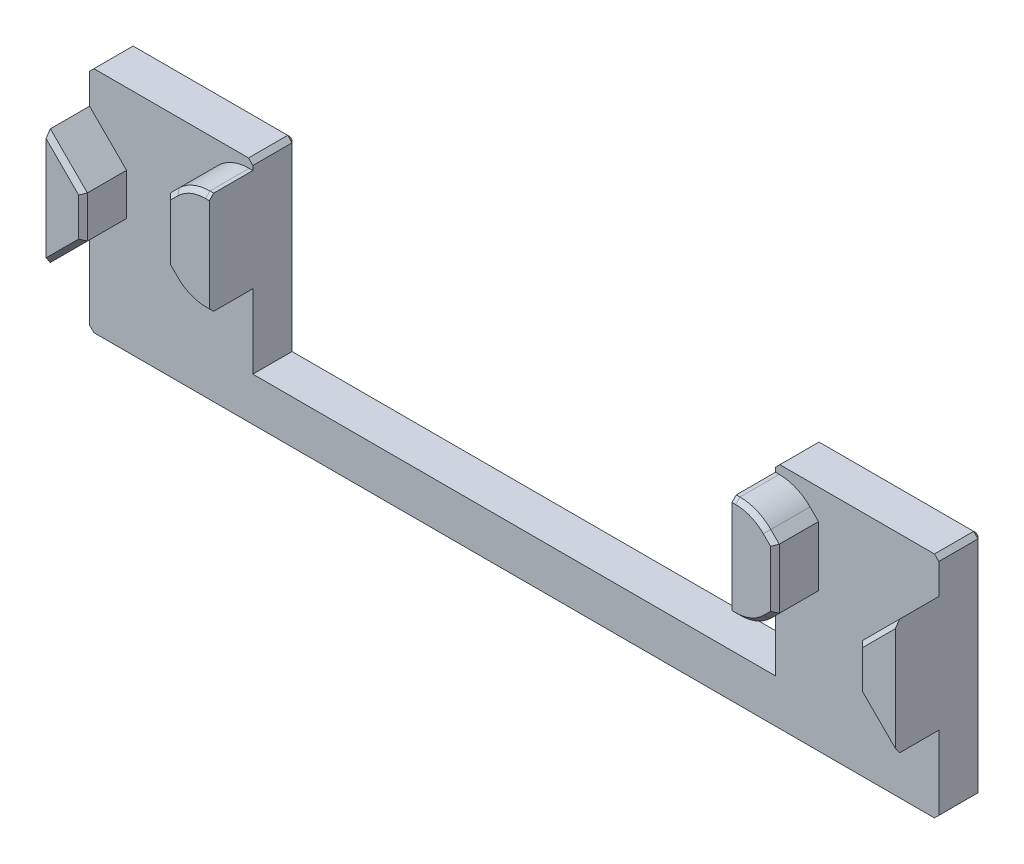
SolidWorks part; units mm, degrees
ref_plane "Front" through (0, 0, 0) normal (0, 0, 1) x (1, 0, 0)
ref_plane "Top" through (0, 0, 0) normal (0, 1, 0) x (1, 0, 0)
ref_plane "Right" through (0, 0, 0) normal (1, 0, 0) x (0, 0, -1)
sketch "Sketch1" plane through (0, 0, 0) normal (0, 0, 1) x (1, 0, 0)
  line L0 (-19.3, -5.25) -> (19.3, -5.25)
  line L5 (19.5, -5.05) -> (19.5, 5.05)
  line L6 (19.3, 5.25) -> (12.2, 5.25)
  line L7 (12, 5.05) -> (12, -3.25)
  line L8 (12, -3.25) -> (-12, -3.25)
  line L9 (-12, -3.25) -> (-12, 5.05)
  line L10 (-12.2, 5.25) -> (-19.3, 5.25)
  line L11 (-19.5, 5.05) -> (-19.5, -5.05)
  line L12 (19.5, 5.05) -> (19.5, -5.05) construction
  line L13 (19.3, 5.25) -> (12, 5.25) construction
  line L14 (19.3, -5.25) -> (-19.3, -5.25) construction
  line L15 (19.5, 5.05) -> (19.3, 5.25)
  line L16 (-12, 5.25) -> (-19.3, 5.25) construction
  line L17 (-19.5, 5.05) -> (-19.5, -5.05) construction
  line L18 (12.2, 5.25) -> (12, 5.05)
  line L19 (19.3, -5.25) -> (19.5, -5.05)
  line L20 (-19.5, -5.05) -> (-19.3, -5.25)
  line L21 (-19.3, 5.25) -> (-19.5, 5.05)
  line L22 (-12, 5.05) -> (-12.2, 5.25)
  point P0 (-19.5, -5.25)
  point P1 (19.5, -5.25)
  point P2 (19.5, 5.25)
  point P4 (12, 5.25)
  point P6 (-19.5, 5.25)
  point P13 (-12, 5.25)
  dimension "D1" = 45
  dimension "D3" = 45
  dimension "D6" = 0.2
  dimension "D5" = 45
  dimension "D7" = 45
  dimension "D12" = 0.2
  dimension "D8" = 45
  dimension "D11" = 0.2
  dimension "D9" = 0.2
  dimension "D10" = 45
  dimension "D2" = 0.2
  dimension "D4" = 0.2
extrude "Boss-Extrude1" add sketch "Sketch1" against normal blind 2
sketch "Sketch3" plane through (0, 0, 0) normal (0, 0, 1) x (1, 0, 0)
  line L12 (12, 4.85) -> (12, 0.15)
  line L13 (12, 5.05) -> (12, -3.25) construction
  line L20 (13.975, 1.125) -> (13.975, 3.875)
  line L24 (13.975, 3.875) -> (13.5858, 4.2642)
  line L26 (12.1716, 4.85) -> (11.3284, 4.85)
  line L28 (9.9142, 4.2642) -> (9.5, 3.85)
  line L30 (9.5, 3.85) -> (9.5, 1.15)
  line L32 (9.5, 1.15) -> (9.9142, 0.7358)
  line L36 (11.3284, 0.15) -> (12.1716, 0.15)
  line L37 (13.5858, 0.7358) -> (13.975, 1.125)
  line L38 (13.975, 1.125) -> (13.975, 3.875)
  line L39 (13.975, 3.875) -> (13.5858, 4.2642)
  line L40 (12.1716, 4.85) -> (11.3284, 4.85)
  line L41 (9.9142, 4.2642) -> (9.5, 3.85)
  line L42 (9.5, 3.85) -> (9.5, 1.15)
  line L43 (9.5, 1.15) -> (9.9142, 0.7358)
  line L44 (11.3284, 0.15) -> (12.1716, 0.15)
  line L45 (13.5858, 0.7358) -> (13.975, 1.125)
  arc A10 (13.5858, 4.2642) -> (12.1716, 4.85) centre (12.1716, 2.85) ccw
  arc A11 (11.3284, 4.85) -> (9.9142, 4.2642) centre (11.3284, 2.85) ccw
  arc A12 (9.9142, 0.7358) -> (11.3284, 0.15) centre (11.3284, 2.15) ccw
  arc A13 (12.1716, 0.15) -> (13.5858, 0.7358) centre (12.1716, 2.15) ccw
  arc A14 (13.5858, 4.2642) -> (12.1716, 4.85) centre (12.1716, 2.85) ccw
  arc A15 (11.3284, 4.85) -> (9.9142, 4.2642) centre (11.3284, 2.85) ccw
  arc A16 (9.9142, 0.7358) -> (11.3284, 0.15) centre (11.3284, 2.15) ccw
  arc A17 (12.1716, 0.15) -> (13.5858, 0.7358) centre (12.1716, 2.15) ccw
  dimension "D1" = 0
extrude "Slot Aligner" add sketch "Sketch3" along normal blind 2 contours L44 A17 L45 L38 L39 A14 L40 A15 L12 A16 region at (12.9111, 2.5, 0)
mirror "Mirror3" about plane through (0, 0, 0) normal (1, 0, 0) of "Slot Aligner"
sketch "Sketch4" plane through (0, 0, 0) normal (0, 0, 1) x (1, 0, 0)
  line L4 (19.4, 3.5586) -> (19.5, 3.6586)
  line L5 (19.5, 3.8) -> (19.5, -1.8) construction
  line L6 (19.5, 3.6586) -> (19.5, -1.6586)
  line L7 (19.5, -1.6586) -> (19.4, -1.5586)
  line L8 (19.4, -1.5586) -> (19.4, 3.5586)
  line L9 (19.4, 3.5586) -> (17.8, 1.9586)
  line L10 (17.8, 1.9586) -> (17.8, 0.0414)
  line L11 (17.8, 0.0414) -> (19.4, -1.5586)
  line L12 (19.4, -1.5586) -> (19.4, 3.5586) construction
  line L13 (19.4, 3.5586) -> (17.8, 1.9586)
  line L14 (17.8, 1.9586) -> (17.8, 0.0414)
  line L15 (17.8, 0.0414) -> (19.4, -1.5586)
  dimension "D1" = 0.1
extrude "Aligner" add sketch "Sketch4" along normal blind 2
mirror "Aligners" about plane through (0, 0, 0) normal (1, 0, 0) of "Aligner"
chamfer "Deburs" distance 0.2 angle 45 34 edges at (12, 0.9, -2) (12.1, 5.15, -2) (15.75, 5.25, -2) (19.4, 5.15, -2) (19.5, 0, -2) (19.4, -5.15, -2) (0, -5.25, -2) (-19.4, -5.15, -2) (-19.5, 0, -2) (-19.4, 5.15, -2) (-15.75, 5.25, -2) (-12.1, 5.15, -2) (-12, 0.9, -2) (0, -3.25, -2) (-18.65, 2.8086, 2) (-18.65, -0.8086, 2) (-17.8, 1, 2) (18.65, -0.8086, 2) (17.8, 1, 2) (18.65, 2.8086, 2) (-12.0858, 4.85, 2) (-12.0858, 0.15, 2) (-12.9369, 4.6978, 2) (-12.9369, 0.3022, 2) (-13.7804, 4.0696, 2) (-13.7804, 0.9304, 2) (-13.975, 2.5, 2) (12.0858, 4.85, 2) (12.0858, 0.15, 2) (12.9369, 4.6978, 2) (12.9369, 0.3022, 2) (13.7804, 4.0696, 2) (13.975, 2.5, 2) (13.7804, 0.9304, 2)
